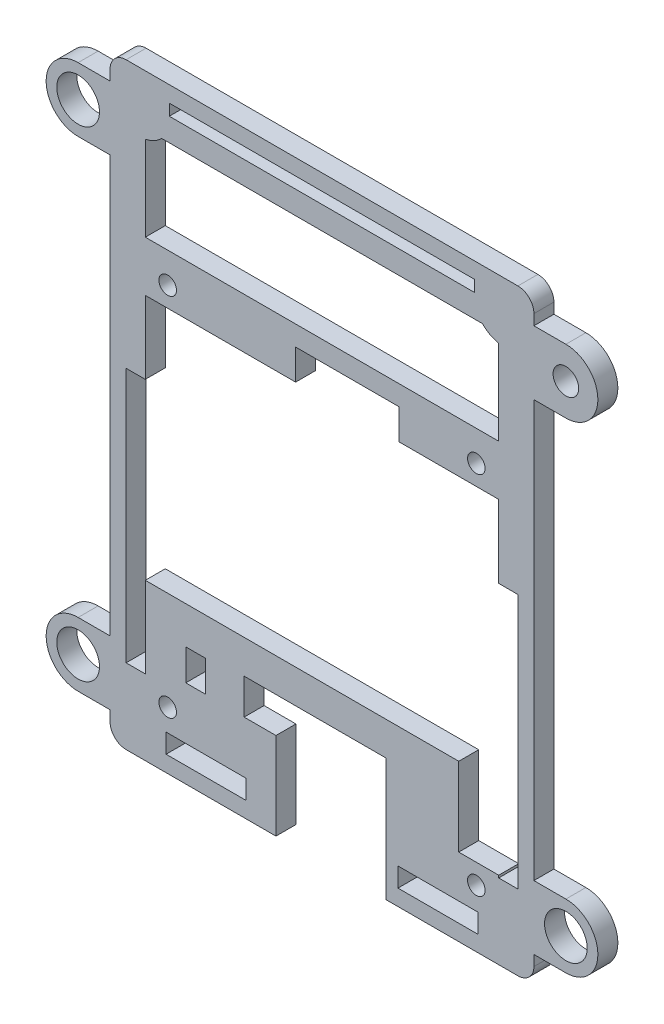
SolidWorks part; units mm, degrees
ref_plane "Front Plane" through (0, 0, 0) normal (0, 0, 1) x (1, 0, 0)
ref_plane "Top Plane" through (0, 0, 0) normal (0, 1, 0) x (1, 0, 0)
ref_plane "Right Plane" through (0, 0, 0) normal (1, 0, 0) x (0, 0, -1)
sketch "Sketch1" plane through (0, 0, 0) normal (0, 0, 1) x (1, 0, 0)
  line L0 (38.227, 0) -> (38.227, 13.8938)
  line L1 (52.832, 0) -> (40.132, 0) construction
  line L2 (38.227, 13.8938) -> (17.907, 13.8938)
  line L3 (17.907, 13.8938) -> (17.907, 8.255)
  line L4 (17.907, 8.255) -> (22.9616, 8.255)
  line L5 (22.9616, 8.255) -> (22.9616, 0)
  line L6 (40.132, 0) -> (16.002, 0) construction
  line L8 (0, 19.2278) -> (49.784, 19.2278)
  line L9 (49.784, 19.2278) -> (49.784, 6.731)
  line L10 (49.784, 6.731) -> (56.134, 6.731)
  line L11 (52.578, 6.731) -> (56.134, 6.731) construction
  line L12 (16.002, 0) -> (3.302, 0) construction
  line L13 (6.4262, 13.2842) -> (9.6012, 13.2842)
  line L14 (6.4262, 13.2842) -> (6.4262, 8.3312)
  line L15 (6.4262, 8.3312) -> (9.6012, 8.3312)
  line L16 (9.6012, 13.2842) -> (9.6012, 8.3312)
  line L17 (0, 6.35) -> (0, -3.048) construction
  line L18 (0, 6.35) -> (0, 46.863) construction
  line L19 (16.002, -3.048) -> (16.002, 0) construction
  line L20 (16.002, -3.048) -> (3.302, -3.048) construction
  line L21 (3.302, -3.048) -> (3.302, 0) construction
  line L22 (40.132, -3.048) -> (40.132, 0) construction
  line L23 (52.832, -3.048) -> (40.132, -3.048) construction
  line L24 (52.832, -3.048) -> (52.832, 0) construction
  line L25 (59.182, 6.35) -> (56.134, 6.35) construction
  line L28 (59.182, 46.863) -> (56.134, 46.863) construction
  line L29 (-3.048, 46.863) -> (0, 46.863) construction
  line L30 (-3.048, 6.35) -> (-3.048, 46.863) construction
  line L31 (-3.048, 6.35) -> (0, 6.35) construction
  line L32 (16.002, -3.048) -> (16.002, 0)
  line L33 (16.002, -3.048) -> (3.302, -3.048)
  line L34 (3.302, -3.048) -> (3.302, 0)
  line L35 (16.002, 0) -> (3.302, 0)
  line L36 (40.132, -3.048) -> (40.132, 0)
  line L37 (52.832, -3.048) -> (40.132, -3.048)
  line L38 (52.832, 0) -> (40.132, 0)
  line L39 (52.832, -3.048) -> (52.832, 0)
  line L40 (59.182, 6.35) -> (56.134, 6.35)
  line L41 (59.182, 46.863) -> (59.182, 6.35)
  line L42 (56.134, 46.863) -> (56.134, 6.35)
  line L43 (59.182, 46.863) -> (56.134, 46.863)
  line L44 (-3.048, 46.863) -> (0, 46.863)
  line L45 (0, 6.35) -> (0, 46.863)
  line L46 (-3.048, 6.35) -> (-3.048, 46.863)
  line L47 (-3.048, 6.35) -> (0, 6.35)
  line L48 (59.182, -5.588) -> (-3.048, -5.588) construction
  line L49 (59.182, -5.588) -> (-3.048, -5.588)
  line L50 (-5.588, -3.048) -> (-5.588, 86.7664)
  line L51 (61.722, -3.048) -> (61.722, 86.7664)
  line L52 (0, 66.421) -> (56.134, 66.421)
  line L53 (3.556, 58.42) -> (0, 58.42) construction
  line L54 (52.578, 58.42) -> (56.134, 58.42) construction
  line L55 (3.556, 58.42) -> (0, 58.42)
  line L56 (52.578, 58.42) -> (56.134, 58.42)
  line L57 (3.556, 58.42) -> (23.876, 58.42)
  line L58 (23.876, 58.42) -> (23.876, 63.246)
  line L59 (23.876, 63.246) -> (40.259, 63.246)
  line L60 (40.259, 63.246) -> (40.259, 58.42)
  line L61 (40.259, 58.42) -> (52.578, 58.42)
  line L63 (-3.048, 89.3064) -> (59.182, 89.3064)
  line L64 (0, 83.2104) -> (56.134, 83.2104)
  line L67 (0, 46.863) -> (0, 83.2104)
  line L68 (56.134, 83.2104) -> (56.134, 46.863)
  line L69 (0, 83.2104) -> (0, 46.863)
  line L70 (3.81, 86.7664) -> (52.324, 86.7664)
  line L71 (3.81, 86.7664) -> (3.81, 84.963)
  line L72 (3.81, 84.963) -> (52.324, 84.963)
  line L73 (52.324, 86.7664) -> (52.324, 84.963)
  line L74 (56.134, 83.2104) -> (56.134, 46.863)
  line L76 (38.227, 0) -> (38.227, -5.588)
  line L77 (22.9616, 0) -> (22.9616, -5.588)
  circle A0 centre (3.556, 3.556) radius 1.397 construction
  circle A1 centre (52.578, 3.556) radius 1.397 construction
  circle A2 centre (3.556, 61.595) radius 1.397 construction
  circle A3 centre (52.578, 61.595) radius 1.397 construction
  circle A4 centre (3.556, 3.556) radius 1.397
  circle A5 centre (52.578, 3.556) radius 1.397
  circle A6 centre (3.556, 61.595) radius 1.397
  circle A7 centre (52.578, 61.595) radius 1.397
  arc A8 (-5.588, -3.048) -> (-3.048, -5.588) centre (-3.048, -3.048) ccw construction
  arc A9 (59.182, -5.588) -> (61.722, -3.048) centre (59.182, -3.048) ccw construction
  arc A10 (-5.588, -3.048) -> (-3.048, -5.588) centre (-3.048, -3.048) ccw
  arc A11 (59.182, -5.588) -> (61.722, -3.048) centre (59.182, -3.048) ccw
  arc A12 (59.182, 89.3064) -> (61.722, 86.7664) centre (59.182, 86.7664) cw
  arc A13 (-5.588, 86.7664) -> (-3.048, 89.3064) centre (-3.048, 86.7664) cw
  point P74 (-5.588, 89.3064)
  dimension "D12" = 3.429
  dimension "D17" = 2.54
  dimension "D1" = 20.32
  dimension "D3" = 15.2654
  dimension "D4" = 8.255
  dimension "D5" = 19.4818
  dimension "D6" = 5.334
  dimension "D7" = 3.175
  dimension "D8" = 4.953
  dimension "D9" = 8.3312
  dimension "D10" = 6.4262
  dimension "D11" = 6.35
  dimension "D13" = 23.495
  dimension "D14" = 23.876
  dimension "D15" = 3.175
  dimension "D16" = 1.8034
  dimension "D18" = 3.556
  dimension "D19" = 3.81
  dimension "D20" = 3.81
  dimension "D21" = 15.875
  dimension "D22" = 16.7894
extrude "Boss-Extrude1" add sketch "Sketch1" along normal blind 3.175 contours L60 L61 L56 L52 L45 L55 L57 L58 L59 A7 A6 | A13 L50 A10 L49 A11 L51 A12 L63 A5 A4 L70 L73 L72 L71 L13 L16 L15 L14 L35 L32 L33 L34 L39 L37 L36 L38 L40 L10 L9 L8 L45 L47 region at (39.3904, 6.9469, 0) region at (0.567, 62.4205, 0)
sketch "Sketch2" plane through (0, 0, 3.175) normal (0, 0, 1) x (1, 0, 0)
  line L0 (-5.588, -3.048) -> (-5.588, 86.7664) construction
  line L1 (-3.048, 89.3064) -> (59.182, 89.3064) construction
  line L2 (61.722, -3.048) -> (61.722, 86.7664) construction
  line L3 (0, 81.3054) -> (56.134, 81.3054)
  line L4 (0, 66.421) -> (0, 83.2104) construction
  line L5 (56.134, 83.2104) -> (56.134, 66.421) construction
  line L6 (0, 79.9092) -> (0, 83.2104)
  line L7 (0, 83.2104) -> (56.134, 83.2104)
  line L8 (56.134, 83.2104) -> (56.134, 79.9092)
  circle A0 centre (-0.8509, 84.5693) radius 4.7371
  circle A1 centre (56.9849, 84.5693) radius 4.7371
  dimension "D1" = 9.4742
  dimension "D2" = 8.001
extrude "Boss-Extrude2" add sketch "Sketch2" against normal up to vertex (3.175 mm away) contours L3 A0 L7 L6 | L6 A0 L3 | A1 L7 A0 L3 | L7 A1 L3 L8 | L3 A1 L8 region at (1.6331, 82.3113, 3.175) region at (0.9571, 80.7762, 3.175) region at (28.067, 82.2509, 3.175) region at (54.5009, 82.3113, 3.175) region at (55.1769, 80.7762, 3.175) up to point (0, 83.2104, 0)
sketch "Sketch3" plane through (0, 0, 3.175) normal (0, 0, 1) x (1, 0, 0)
  line L0 (20.7518, 8.255) -> (20.7518, -5.588)
  line L3 (17.907, 8.255) -> (22.9616, 8.255) construction
  line L4 (22.9616, -5.588) -> (-3.048, -5.588) construction
  line L5 (17.907, 13.8938) -> (15.6972, 13.8938)
  line L6 (15.6972, 13.8938) -> (15.6972, 8.255)
  line L7 (15.6972, 8.255) -> (17.907, 8.255)
  line L8 (17.907, 13.8938) -> (17.907, 8.255)
  line L9 (20.7518, 8.255) -> (22.9616, 8.255)
  line L10 (22.9616, 8.255) -> (22.9616, -5.588)
  line L11 (22.9616, -5.588) -> (20.7518, -5.588)
  dimension "D1" = 2.2098
  dimension "D2" = 2.2098
extrude "Cut-Extrude1" cut sketch "Sketch3" against normal through all
sketch "Sketch4" plane through (0, 0, 3.175) normal (0, 0, 1) x (1, 0, 0)
  line B0 (6.4923, 13.2132) -> (9.6673, 13.2132)
  line B1 (6.4923, 13.2132) -> (6.4923, 8.2602)
  line B2 (9.6673, 13.2132) -> (9.6673, 8.2602)
  line B3 (6.4923, 8.2602) -> (9.6673, 8.2602)
  line B4 (15.7369, 13.9566) -> (15.7369, 8.184)
  line B5 (15.7369, 8.184) -> (20.781, 8.184)
  line B6 (38.329, 13.9566) -> (15.7369, 13.9566)
  line B7 (38.329, -5.5096) -> (38.329, 13.9566)
  line B8 (20.781, 8.184) -> (20.781, -5.5096)
  circle B9 centre (3.6221, 3.485) radius 1.397
  circle B10 centre (52.6441, 3.485) radius 1.397
sketch_block_instance "Block2-1"
sketch_block "Block2"
sketch "Sketch5" plane through (0, 0, 3.175) normal (0, 0, 1) x (1, 0, 0)
  line L0 (-10.668, 3.7021) -> (66.802, 3.7021) construction
  line L1 (66.802, 3.7021) -> (66.802, 80.0164) construction
  line L2 (66.802, 80.0164) -> (-10.668, 80.0163) construction
  line L3 (-10.668, 80.0163) -> (-10.668, 3.7021) construction
  line L4 (-10.668, 41.8592) -> (-5.588, 41.8592) construction
  line L5 (-5.588, -3.048) -> (-5.588, 86.7664) construction
  line L6 (61.722, 41.8592) -> (66.802, 41.8592) construction
  line L7 (61.722, -3.048) -> (61.722, 86.7664) construction
  line L8 (-10.668, 85.0964) -> (-5.588, 85.0964)
  line L9 (-10.668, 74.9364) -> (-5.588, 74.9364)
  line L10 (-10.668, 8.782) -> (-5.588, 8.782)
  line L11 (-10.668, -1.378) -> (-5.588, -1.378)
  line L12 (66.802, -1.3779) -> (61.722, -1.3779)
  line L13 (66.802, 74.9363) -> (61.722, 74.9363)
  line L14 (66.802, 8.7821) -> (61.722, 8.7821)
  line L15 (66.802, 85.0964) -> (61.722, 85.0964)
  line L16 (-5.588, 85.0964) -> (-5.588, 74.9364)
  line L17 (61.722, 85.0964) -> (61.722, 74.9363)
  line L18 (61.722, 74.9363) -> (60.7051, 74.5489)
  line L19 (61.722, -1.3779) -> (61.722, 8.7821)
  line L20 (-5.588, 8.782) -> (-5.588, -1.378)
  circle A0 centre (66.802, 80.0164) radius 2.032
  circle A1 centre (66.802, 3.7021) radius 3.3909
  circle A2 centre (-10.668, 3.7021) radius 3.3909
  circle A3 centre (-10.668, 80.0163) radius 3.3909
  circle A4 centre (-10.668, 3.7021) radius 5.08
  circle A5 centre (-10.668, 80.0163) radius 5.08
  circle A6 centre (66.802, 80.0164) radius 5.08
  circle A7 centre (66.802, 3.7021) radius 5.08
  dimension "D1" = 70.6882
  dimension "D2" = 70.8914
  dimension "D3" = 4.064
  dimension "D4" = 10.16
extrude "Boss-Extrude3" add sketch "Sketch5" against normal up to vertex (3.175 mm away) contours A4 L20 L10 | A4 L11 L20 | A4 A2 | A7 A1 | A7 L19 L12 | A7 L14 L19 | A6 A0 | A6 L17 L13 | A6 L15 L17 | A5 L9 L16 | A5 A3 | A5 L16 L8 region at (-6.7227, 83.9616, 3.175) region at (-7.1775, 83.5069, 3.175) region at (-6.7227, 76.0711, 3.175) region at (-6.7227, 7.6473, 3.175) region at (-7.1775, 7.1926, 3.175) region at (-6.7227, -0.2432, 3.175) region at (63.3115, 0.2115, 3.175) region at (62.8567, -0.2432, 3.175) region at (62.8567, 7.6473, 3.175) region at (63.3115, 76.5258, 3.175) region at (62.8567, 76.0711, 3.175) region at (62.8567, 83.9616, 3.175) up to point (-5.588, 86.7664, 0)
